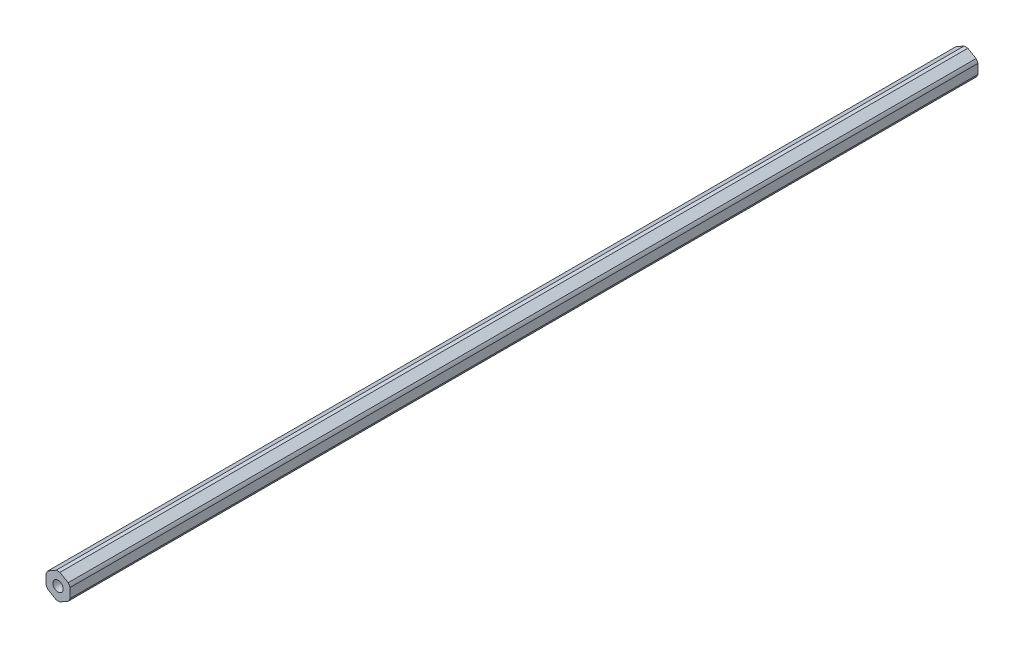
SolidWorks part; units mm, degrees
material "7075-T6 (SN)"
ref_plane "Front Plane" through (0, 0, 0) normal (0, 0, 1) x (1, 0, 0)
ref_plane "Top Plane" through (0, 0, 0) normal (0, 1, 0) x (1, 0, 0)
ref_plane "Right Plane" through (0, 0, 0) normal (1, 0, 0) x (0, 0, -1)
sketch "Sketch1" plane through (0, 0, 0) normal (0, 0, 1) x (1, 0, 0)
  line L0 (0, 5.4993) -> (-0.7417, 5.071) construction
  line L1 (-0.7417, 5.071) -> (-4.0208, 3.1778)
  line L2 (-4.7625, 1.8932) -> (-4.7625, -1.8932)
  line L3 (-4.0208, -3.1778) -> (-0.7417, -5.071)
  line L4 (0.7417, -5.071) -> (4.0208, -3.1778)
  line L5 (4.7625, -1.8932) -> (4.7625, 1.8932)
  line L6 (4.0208, 3.1778) -> (0.7417, 5.071)
  line L7 (0.7417, 5.071) -> (0, 5.4993) construction
  line L8 (4.7625, 2.7496) -> (4.0208, 3.1778) construction
  line L9 (4.7625, 1.8932) -> (4.7625, 2.7496) construction
  line L10 (4.0208, -3.1778) -> (4.7625, -2.7496) construction
  line L11 (4.7625, -2.7496) -> (4.7625, -1.8932) construction
  line L12 (-0.7417, -5.071) -> (0, -5.4993) construction
  line L13 (0, -5.4993) -> (0.7417, -5.071) construction
  line L14 (-4.7625, -1.8932) -> (-4.7625, -2.7496) construction
  line L15 (-4.7625, -2.7496) -> (-4.0208, -3.1778) construction
  line L16 (-4.0208, 3.1778) -> (-4.7625, 2.7496) construction
  line L17 (-4.7625, 2.7496) -> (-4.7625, 1.8932) construction
  circle A0 centre (0, 0) radius 4.7625 construction
  arc A1 (0.7417, 5.071) -> (-0.7417, 5.071) centre (0, 0) ccw
  arc A2 (4.0208, 3.1778) -> (0.7417, 5.071) centre (0, 0) ccw construction
  arc A3 (-0.7417, 5.071) -> (-4.0208, 3.1778) centre (0, 0) ccw construction
  arc A4 (-4.0208, 3.1778) -> (-4.7625, 1.8932) centre (0, 0) ccw
  arc A5 (-4.7625, 1.8932) -> (-4.7625, -1.8932) centre (0, 0) ccw construction
  arc A6 (-4.7625, -1.8932) -> (-4.0208, -3.1778) centre (0, 0) ccw
  arc A7 (-4.0208, -3.1778) -> (-0.7417, -5.071) centre (0, 0) ccw construction
  arc A8 (-0.7417, -5.071) -> (0.7417, -5.071) centre (0, 0) ccw
  arc A9 (0.7417, -5.071) -> (4.0208, -3.1778) centre (0, 0) ccw construction
  arc A10 (4.0208, -3.1778) -> (4.0208, 3.1778) centre (0, 0) ccw
  dimension "D1" = 9.525
  dimension "D2" = 10.25
extrude "Boss-Extrude1" add sketch "Sketch1" along normal mid plane 359.029 contours L5 A10 L6 A1 L1 A4 L2 A6 L3 A8 L4 region at (0, 0, 0)
sketch "Sketch2" plane through (0, 0, 179.5145) normal (0, 0, 1) x (1, 0, 0)
  circle A0 centre (0, 0) radius 2.0193
  dimension "D1" = 4.0386
extrude "Cut-Extrude1" cut sketch "Sketch2" against normal through all
